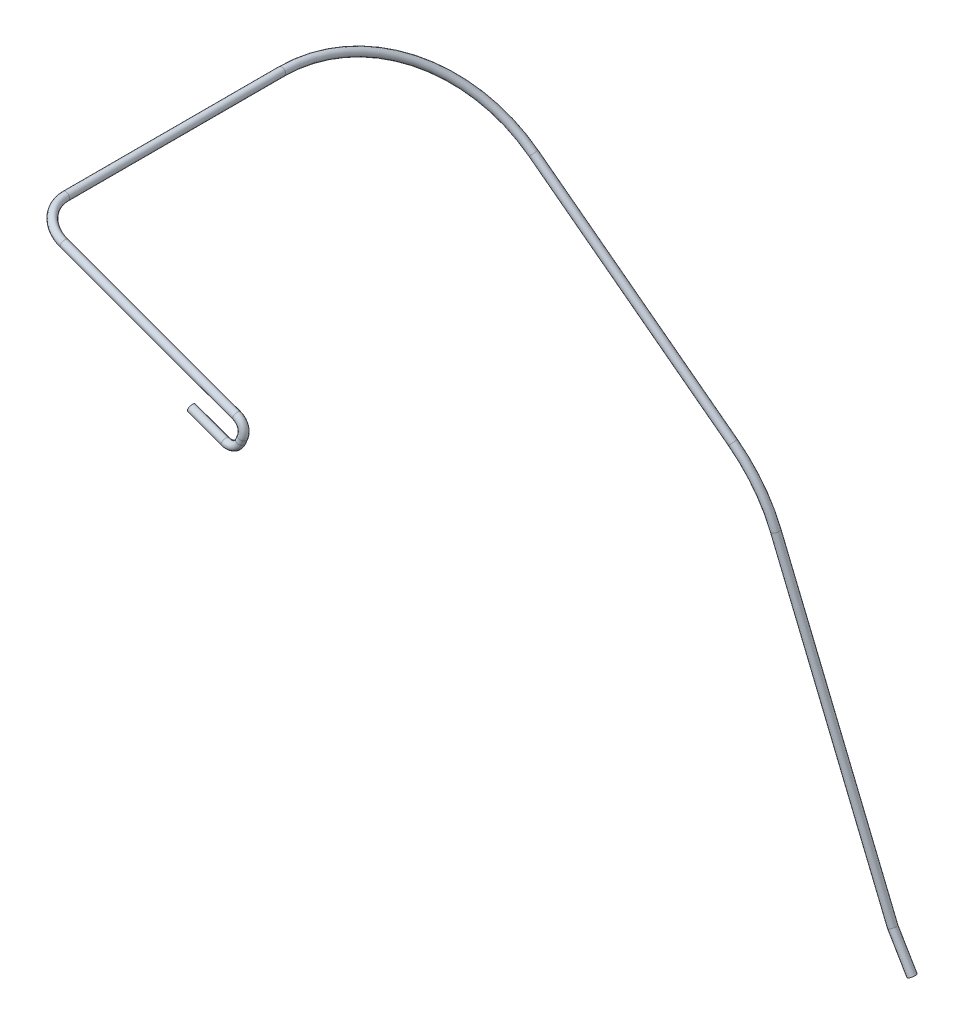
SolidWorks part; units mm, degrees
ref_plane "Front Plane" through (0, 0, 0) normal (0, 0, 1) x (1, 0, 0)
ref_plane "Top Plane" through (0, 0, 0) normal (0, 1, 0) x (1, 0, 0)
ref_plane "Right Plane" through (0, 0, 0) normal (1, 0, 0) x (0, 0, -1)
sketch3d "3DSketch1"
  line L0 (0, 0, 0) -> (101.2069, 0, 0) construction
  line L1 (0, 0, 0) -> (43.4799, -15.8254, 0)
  line L4 (-78.7816, -14.8866, -521.0634) -> (-78.7816, -259.3168, -521.0634) construction
  line L5 (-205.2057, 112.8569, -42.7503) -> (-205.2057, 112.8569, -322.0937)
  line L6 (-78.7816, -14.8866, -521.0634) -> (146.4408, -242.4597, -553.688)
  line L7 (194.347, -321.1555, -561.2564) -> (321.6474, -712.7858, -585.1574)
  line L9 (321.6474, -712.7858, -585.1574) -> (345.0438, -756.9428, -586.8205)
  line L10 (55.7259, 17.8856, -2.7503) -> (-167.6179, 99.1761, -2.7503)
  line L11 (64.725, -1.2462, -1.6077) -> (62.7096, -6.8489, -1.1511)
  arc A0 (-167.6179, 99.1761, -2.7503) -> (-205.2057, 112.8569, -42.7503) centre (-167.6179, 99.1761, -42.7503) ccw
  arc A1 (62.7096, -6.8489, -1.1511) -> (43.4799, -15.8254, 0) centre (48.5952, -1.7712, -1.1468) ccw
  arc A2 (64.725, -1.2462, -1.6077) -> (55.7259, 17.8856, -2.7503) centre (50.6106, 3.8314, -1.6034) ccw
  arc A4 (146.4408, -242.4597, -553.688) -> (194.347, -321.1555, -561.2564) centre (5.7043, -383.821, -539.1896) ccw
  arc A5 (-205.2057, 112.8569, -322.0937) -> (-78.7816, -14.8866, -521.0634) centre (-64.5204, -29.2967, -322.0937) ccw
  point P9 (169.1447, -61.5636, 0)
  point P12 (-205.2057, 112.8569, -2.7503)
  point P13 (-181.2988, 61.5884, -42.7503)
  point P15 (48.2029, -2.8489, -16.1029)
  point P16 (225.5262, -82.0848, 0)
  point P20 (169.1662, 16.1197, -5.4454)
  point P21 (180.0683, -27.3714, -2.7503)
  point P23 (51.0028, 4.9091, 13.3527)
  point P24 (463.976, -835.6715, -608.2609)
  point P28 (179.686, -276.0518, -558.5038)
  point P29 (-18.8775, -379.7006, -737.6304)
  point P32 (-205.2057, 112.8569, -502.7503)
  point P33 (-206.674, -169.982, -322.0937)
  dimension "D8" = 180
  dimension "D9" = 45
  dimension "D10" = 460
  dimension "D11" = 50
  dimension "D2" = 40
  dimension "D3" = 36
  dimension "D4" = 15
  dimension "D13" = 200
  dimension "D1" = 20
  dimension "D5" = 500
  dimension "D6" = 550
  dimension "D7" = 410
  dimension "D12" = 170
sweep "Sweep-Thin1" add path "3DSketch1" circular profile diameter 10 parameters "D1"=1, "D3"=10
